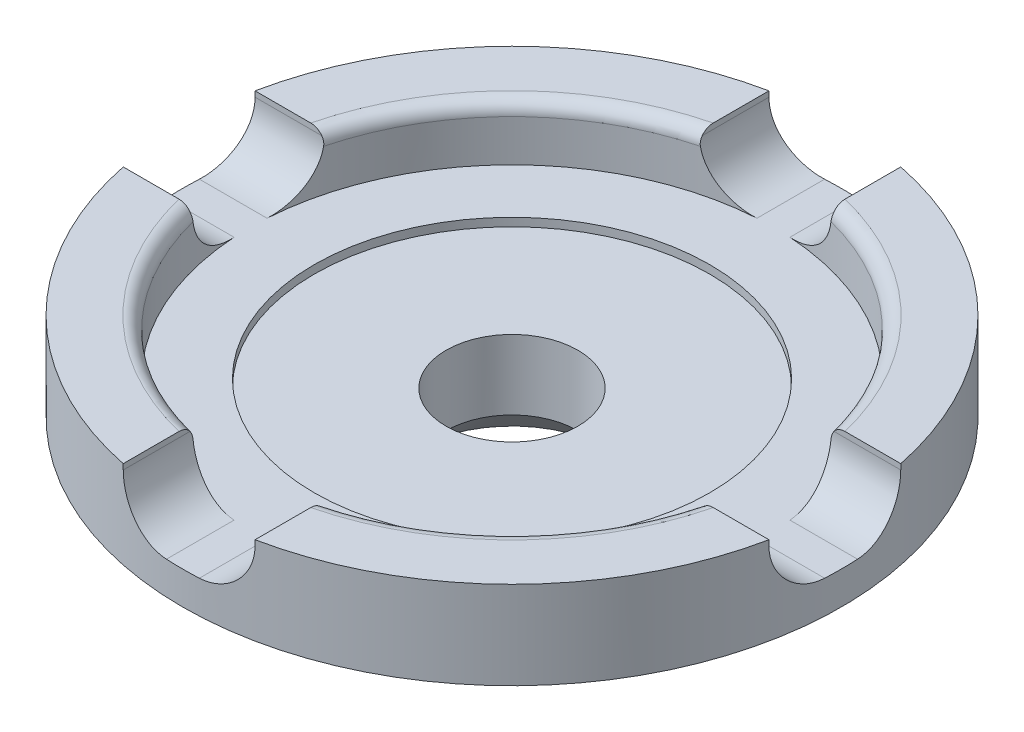
SolidWorks part; units mm, degrees
ref_plane "Front plane" through (0, 0, 0) normal (0, 0, 1) x (1, 0, 0)
ref_plane "Top plane" through (0, 0, 0) normal (0, 1, 0) x (1, 0, 0)
ref_plane "Right plane" through (0, 0, 0) normal (1, 0, 0) x (0, 0, -1)
ref_axis "Axis X" through (0, 0, 0) along (1, 0, 0)
ref_axis "Axis Y" through (0, 0, 0) along (0, 1, 0)
ref_axis "Axis Z" through (0, 0, 0) along (0, 0, 1)
sketch "Sketch1" plane through (0, 0, 0) normal (0, 1, 0) x (1, 0, 0)
  circle A0 centre (0, 0) radius 10
  dimension "D1" = 20
extrude "Extrude1" add sketch "Sketch1" along normal blind 1
sketch "Sketch6" plane through (0, 1, 0) normal (0, 1, 0) x (1, 0, 0)
  line L0 (-2, 9.798) -> (-2, 7.6943)
  line L1 (2, 9.798) -> (2, 7.6943)
  line L2 (0, 10) -> (0, 0) construction
  line L3 (9.798, 2) -> (7.6943, 2)
  line L4 (9.798, -2) -> (7.6943, -2)
  line L5 (2, -9.798) -> (2, -7.6943)
  line L6 (-2, -9.798) -> (-2, -7.6943)
  line L7 (-9.798, -2) -> (-7.6943, -2)
  line L8 (-9.798, 2) -> (-7.6943, 2)
  arc A0 (-2, 7.6943) -> (-7.6943, 2) centre (0, 0) ccw
  arc A1 (-2, 9.798) -> (-9.798, 2) centre (0, 0) ccw
  circle A2 centre (0, 0) radius 10 construction
  arc A3 (7.6943, 2) -> (2, 7.6943) centre (0, 0) ccw
  arc A4 (9.798, 2) -> (2, 9.798) centre (0, 0) ccw
  arc A5 (-7.6943, -2) -> (-2, -7.6943) centre (0, 0) ccw
  arc A6 (-9.798, -2) -> (-2, -9.798) centre (0, 0) ccw
  arc A7 (2, -7.6943) -> (7.6943, -2) centre (0, 0) ccw
  arc A8 (2, -9.798) -> (9.798, -2) centre (0, 0) ccw
  point P11 (2, 8.7461)
  point P27 (0, 0)
  dimension "D1" = 15.9
  dimension "D2" = 4
  dimension "D3" = 4
extrude "Extrude6" add sketch "Sketch6" along normal blind 1.6667
sketch "Sketch9" plane through (0, 1, 0) normal (0, 1, 0) x (1, 0, 0)
  circle A0 centre (0, 0) radius 6
  dimension "D1" = 12
extrude "Extrude9" cut sketch "Sketch9" against normal blind 0.25
sketch "Sketch7" plane through (0, 0, 0) normal (0, -1, 0) x (1, 0, 0)
  circle A0 centre (0, 0) radius 4.9
  dimension "D1" = 9.8
extrude "Extrude7" add sketch "Sketch7" along normal blind 2.3667
sketch "Sketch8" plane through (0, -2.3667, 0) normal (0, -1, 0) x (1, 0, 0)
  circle A0 centre (0, 0) radius 2
  dimension "D1" = 4
extrude "Extrude8" cut sketch "Sketch8" against normal through all
fillet "Fillet2" radius 0.4 5 edges at (0, -2.3667, -4.9) (-5.6215, 2.6667, -5.6215) (-5.6215, 2.6667, 5.6215) (5.6215, 2.6667, 5.6215) (5.6215, 2.6667, -5.6215)
chamfer "Chamfer2" distance 1 angle 45 1 edges at (0, -2.3667, -2)
fillet "Fillet3" radius 1.5 8 edges at (8.7461, 1, 2) (8.7461, 1, -2) (2, 1, -8.7461) (-2, 1, -8.7461) (-2, 1, 8.7461) (2, 1, 8.7461) (-8.7461, 1, 2) (-8.7461, 1, -2)
equation "\"motor_D\"= 30'Motor diameter"
equation "\"motor_H\"= 13'Motor heigh"
equation "\"motor_d1\"= 25.4558'Seating diameter of screws on the fixed part of the motor"
equation "\"motor_s1\"= 2'Screws diameter on the fixed part of motor"
equation "\"motor_d2\"= 0'Seating diameter of screws on the moving part of the motor (if this parameter is not determine, write 0)"
equation "\"motor_a2\"= 10'Seating parameter in rectangle of screws on the moving part of the motor"
equation "\"motor_b2\"= 22'Seating parameter in rectangle of screws on the moving part of the motor"
equation "\"motor_s2\"= 2'Screws diameter on the moving part of motor"
equation "\"motor_cmd\"= 12'Central magnet mount diameter"
equation "\"motor_cmh\"= 1.4'Central magnet mount heigh (if not write 0)"
equation "\"motor_Dc\"= 5'Central hole diameter of motor"
equation "\"motor_whR\"= 10'Distance from center of motor to wires"
equation "\"bearing_d1\"= 8'Bearing inner diameter"
equation "\"bearing_d2\"= 16'Bearing external diameter"
equation "\"bearing h\"= 5'Bearing heigh"
equation "\"pin_d\"= 2'Pin diameter"
equation "\"pin_h\"= 12'Pin heigh"
equation "\"magnet_d1\"= 5'Magnet inner diameter"
equation "\"magnet_d2\"= 9.5'Magnet external diameter"
equation "\"magnet_h\"= 3'Magnet heigh"
equation "\"print_offset\"= 0.2'Offset for printing holes"
equation "\"ft_sensor_d1\"= 9.8"
equation "\"ft_sensor_d2\"= 24.9"
equation "\"ft_sensor_d3\"= 22.6'Inner diameter of "
equation "\"ft_sensor_h\"= 7.1"
equation "\"ft_sensor_whD\" = 5"
equation "\"D1@Sketch1\"=\"bearing_d2\"+4"
equation "\"D1@Sketch6\"=\"bearing_d2\"-\"print_offset\"*0.5"
equation "\"D1@Extrude6\"=\"bearing h\"/3"
equation "\"D1@Sketch7\"=\"ft_sensor_d1\""
equation "\"D1@Extrude7\"=\"ft_sensor_h\"/3"
equation "\"D1@Sketch9\"=(\"bearing_d1\"+\"bearing_d2\")/2"
